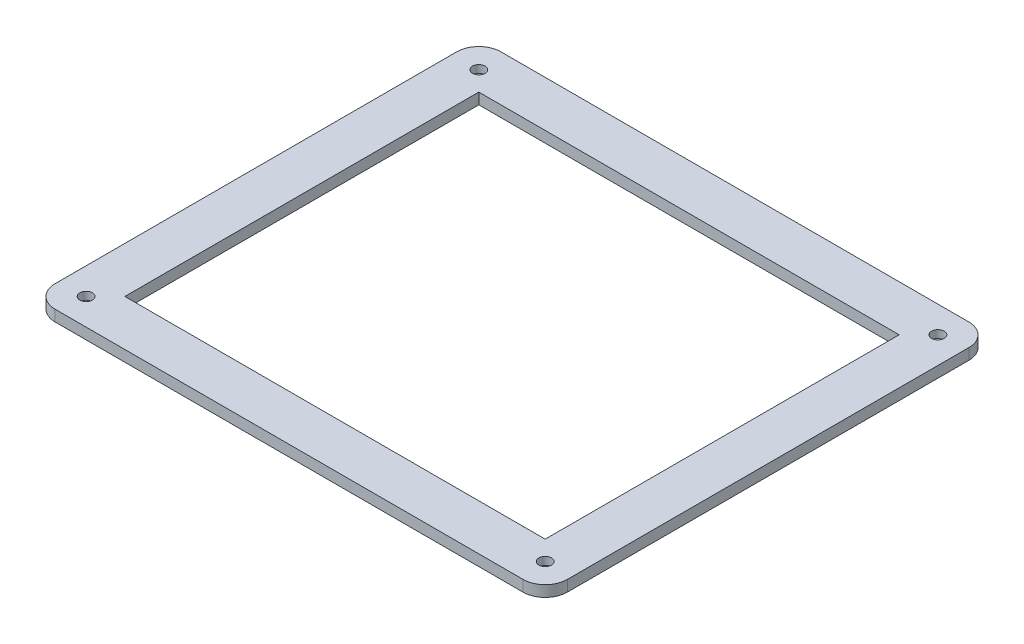
SolidWorks part; units mm, degrees
ref_plane "Front Plane" through (0, 0, 0) normal (0, 0, 1) x (1, 0, 0)
ref_plane "Top Plane" through (0, 0, 0) normal (0, 1, 0) x (1, 0, 0)
ref_plane "Right Plane" through (0, 0, 0) normal (1, 0, 0) x (0, 0, -1)
sketch "Sketch1" plane through (0, 0, 0) normal (0, 1, 0) x (1, 0, 0)
  line L1 (-94.95, 79.95) -> (94.95, 79.95)
  line L2 (-94.95, 79.95) -> (-94.95, -79.95)
  line L3 (-94.95, -79.95) -> (94.95, -79.95)
  line L4 (94.95, 79.95) -> (94.95, -79.95)
  line L5 (-115.7, 100.7) -> (115.7, 100.7)
  line L6 (-115.7, 100.7) -> (-115.7, -100.7)
  line L7 (-115.7, -100.7) -> (115.7, -100.7)
  line L8 (115.7, 100.7) -> (115.7, -100.7)
  point P4 (-94.95, 0)
  point P6 (0, 79.95)
  point P11 (0, -100.7)
  point P12 (-115.7, 0)
  dimension "D1" = 189.9
  dimension "D2" = 159.9
  dimension "D3" = 20.75
  dimension "D4" = 20.75
extrude "Boss-Extrude1" add sketch "Sketch1" along normal blind 5
fillet "Fillet1" radius 10 4 edges at (-115.7, 2.5, -100.7) (115.7, 2.5, -100.7) (115.7, 2.5, 100.7) (-115.7, 2.5, 100.7)
sketch "Sketch2" plane through (0, 0, 0) normal (0, -1, 0) x (1, 0, 0)
  line L0 (-105.7, 100.7) -> (105.7, 100.7) construction
  line L1 (-115.7, -90.7) -> (-115.7, 90.7) construction
  circle A0 centre (-103.7, 88.7) radius 5.85
  dimension "D3" = 11.7
  dimension "D1" = 12
  dimension "D2" = 12
extrude "Boss-Extrude2" add sketch "Sketch2" along normal blind 2.5
sketch "Sketch3" plane through (0, 5, 0) normal (0, 1, 0) x (1, 0, 0)
  line L2 (-115.7, 90.7) -> (-115.7, -90.7) construction
  line L3 (-105.7, -100.7) -> (105.7, -100.7) construction
  circle A0 centre (-103.7, -88.7) radius 1.55
  dimension "D1" = 3.1
  dimension "D2" = 12
  dimension "D3" = 12
extrude "Cut-Extrude1" cut sketch "Sketch3" against normal blind 7.5
sketch "Sketch4" plane through (0, 5, 0) normal (0, 1, 0) x (1, 0, 0)
  circle A0 centre (-103.7, -88.7) radius 2.85
  dimension "D1" = 5.7
extrude "Cut-Extrude2" cut sketch "Sketch4" against normal blind 3.5
mirror "Mirror3" about plane through (0, 0, 0) normal (1, 0, 0) of "Cut-Extrude1", "Cut-Extrude2", "Boss-Extrude2"
mirror "Mirror4" about plane through (0, 0, 0) normal (0, 0, 1) of "Mirror3"
sketch "Sketch5" plane through (0, 5, 0) normal (0, 1, 0) x (1, 0, 0)
  line L0 (-94.95, -79.95) -> (94.95, -79.95) construction
  line L1 (-115.7, 90.7) -> (-115.7, -90.7) construction
  circle A0 centre (-90, -86.9) radius 1.75
  circle A1 centre (-90, -92.9) radius 1.75
  circle A4 centre (-84, -86.9) radius 1.75
  circle A5 centre (-84, -92.9) radius 1.75
  circle A7 centre (-78, -86.9) radius 1.75
  circle A8 centre (-78, -92.9) radius 1.75
  circle A10 centre (-72, -86.9) radius 1.75
  circle A11 centre (-72, -92.9) radius 1.75
  circle A13 centre (-66, -86.9) radius 1.75
  circle A14 centre (-66, -92.9) radius 1.75
  circle A16 centre (-60, -86.9) radius 1.75
  circle A17 centre (-60, -92.9) radius 1.75
  circle A19 centre (-54, -86.9) radius 1.75
  circle A20 centre (-54, -92.9) radius 1.75
  circle A22 centre (-48, -86.9) radius 1.75
  circle A23 centre (-48, -92.9) radius 1.75
  circle A25 centre (-42, -86.9) radius 1.75
  circle A26 centre (-42, -92.9) radius 1.75
  circle A28 centre (-36, -86.9) radius 1.75
  circle A29 centre (-36, -92.9) radius 1.75
  circle A31 centre (-30, -86.9) radius 1.75
  circle A32 centre (-30, -92.9) radius 1.75
  circle A34 centre (-24, -86.9) radius 1.75
  circle A35 centre (-24, -92.9) radius 1.75
  circle A37 centre (-18, -86.9) radius 1.75
  circle A38 centre (-18, -92.9) radius 1.75
  circle A40 centre (-12, -86.9) radius 1.75
  circle A41 centre (-12, -92.9) radius 1.75
  circle A43 centre (-6, -86.9) radius 1.75
  circle A44 centre (-6, -92.9) radius 1.75
  circle A46 centre (0, -86.9) radius 1.75
  circle A47 centre (0, -92.9) radius 1.75
  circle A49 centre (6, -86.9) radius 1.75
  circle A50 centre (6, -92.9) radius 1.75
  circle A52 centre (12, -86.9) radius 1.75
  circle A53 centre (12, -92.9) radius 1.75
  circle A55 centre (18, -86.9) radius 1.75
  circle A56 centre (18, -92.9) radius 1.75
  circle A58 centre (24, -86.9) radius 1.75
  circle A59 centre (24, -92.9) radius 1.75
  circle A61 centre (30, -86.9) radius 1.75
  circle A62 centre (30, -92.9) radius 1.75
  circle A64 centre (36, -86.9) radius 1.75
  circle A65 centre (36, -92.9) radius 1.75
  circle A67 centre (42, -86.9) radius 1.75
  circle A68 centre (42, -92.9) radius 1.75
  circle A70 centre (48, -86.9) radius 1.75
  circle A71 centre (48, -92.9) radius 1.75
  circle A73 centre (54, -86.9) radius 1.75
  circle A74 centre (54, -92.9) radius 1.75
  circle A76 centre (60, -86.9) radius 1.75
  circle A77 centre (60, -92.9) radius 1.75
  circle A79 centre (66, -86.9) radius 1.75
  circle A80 centre (66, -92.9) radius 1.75
  circle A82 centre (72, -86.9) radius 1.75
  circle A83 centre (72, -92.9) radius 1.75
  circle A85 centre (78, -86.9) radius 1.75
  circle A86 centre (78, -92.9) radius 1.75
  circle A88 centre (84, -86.9) radius 1.75
  circle A89 centre (84, -92.9) radius 1.75
  circle A91 centre (90, -86.9) radius 1.75
  circle A92 centre (90, -92.9) radius 1.75
  circle A135 centre (108, -86.9) radius 1.75 [skipped]
  circle A136 centre (108, -92.9) radius 1.75 [skipped]
  circle A137 centre (102, -86.9) radius 1.75 [skipped]
  circle A138 centre (102, -92.9) radius 1.75 [skipped]
  circle A139 centre (96, -86.9) radius 1.75 [skipped]
  circle A140 centre (96, -92.9) radius 1.75 [skipped]
  dimension "D1" = 3.5
  dimension "D4" = 6
  dimension "D2" = 25.7
  dimension "D3" = 6
  dimension "D5" = 6.95
  dimension "D6" = 34
sketch "Sketch6" plane through (0, 5, 0) normal (0, 1, 0) x (1, 0, 0)
  line L1 (-115.7, 90.7) -> (-115.7, -90.7) construction
  circle A1 centre (-102, -75) radius 1.75
  circle A2 centre (-108, -75) radius 1.75
  circle A3 centre (-103.7, -88.7) radius 2.85 construction
  circle A5 centre (-102, -69) radius 1.75
  circle A6 centre (-108, -69) radius 1.75
  circle A8 centre (-102, -63) radius 1.75
  circle A9 centre (-108, -63) radius 1.75
  circle A11 centre (-102, -57) radius 1.75
  circle A12 centre (-108, -57) radius 1.75
  circle A14 centre (-102, -51) radius 1.75
  circle A15 centre (-108, -51) radius 1.75
  circle A17 centre (-102, -45) radius 1.75
  circle A18 centre (-108, -45) radius 1.75
  circle A20 centre (-102, -39) radius 1.75
  circle A21 centre (-108, -39) radius 1.75
  circle A23 centre (-102, -33) radius 1.75
  circle A24 centre (-108, -33) radius 1.75
  circle A26 centre (-102, -27) radius 1.75
  circle A27 centre (-108, -27) radius 1.75
  circle A29 centre (-102, -21) radius 1.75
  circle A30 centre (-108, -21) radius 1.75
  circle A32 centre (-102, -15) radius 1.75
  circle A33 centre (-108, -15) radius 1.75
  circle A35 centre (-102, -9) radius 1.75
  circle A36 centre (-108, -9) radius 1.75
  circle A38 centre (-102, -3) radius 1.75
  circle A39 centre (-108, -3) radius 1.75
  circle A41 centre (-102, 3) radius 1.75
  circle A42 centre (-108, 3) radius 1.75
  circle A44 centre (-102, 9) radius 1.75
  circle A45 centre (-108, 9) radius 1.75
  circle A47 centre (-102, 15) radius 1.75
  circle A48 centre (-108, 15) radius 1.75
  circle A50 centre (-102, 21) radius 1.75
  circle A51 centre (-108, 21) radius 1.75
  circle A53 centre (-102, 27) radius 1.75
  circle A54 centre (-108, 27) radius 1.75
  circle A56 centre (-102, 33) radius 1.75
  circle A57 centre (-108, 33) radius 1.75
  circle A59 centre (-102, 39) radius 1.75
  circle A60 centre (-108, 39) radius 1.75
  circle A62 centre (-102, 45) radius 1.75
  circle A63 centre (-108, 45) radius 1.75
  circle A65 centre (-102, 51) radius 1.75
  circle A66 centre (-108, 51) radius 1.75
  circle A68 centre (-102, 57) radius 1.75
  circle A69 centre (-108, 57) radius 1.75
  circle A71 centre (-102, 63) radius 1.75
  circle A72 centre (-108, 63) radius 1.75
  circle A74 centre (-102, 69) radius 1.75
  circle A75 centre (-108, 69) radius 1.75
  circle A77 centre (-102, 75) radius 1.75
  circle A78 centre (-108, 75) radius 1.75
  circle A116 centre (-102, 93) radius 1.75 [skipped]
  circle A117 centre (-108, 93) radius 1.75 [skipped]
  circle A118 centre (-102, 87) radius 1.75 [skipped]
  circle A119 centre (-108, 87) radius 1.75 [skipped]
  circle A120 centre (-102, 81) radius 1.75 [skipped]
  circle A121 centre (-108, 81) radius 1.75 [skipped]
  dimension "D4" = 13.7
  dimension "D1" = 7.7
  dimension "D2" = 6
  dimension "D7" = 29
